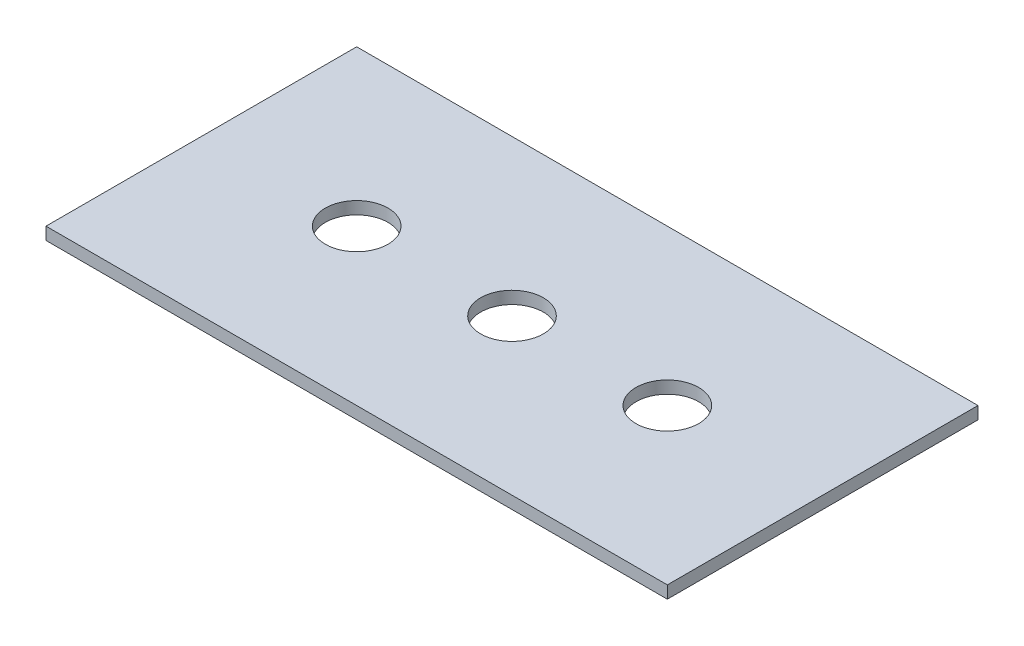
SolidWorks part; units mm, degrees
ref_plane "Front Plane" through (0, 0, 0) normal (0, 0, 1) x (1, 0, 0)
ref_plane "Top Plane" through (0, 0, 0) normal (0, 1, 0) x (1, 0, 0)
ref_plane "Right Plane" through (0, 0, 0) normal (1, 0, 0) x (0, 0, -1)
sketch "Sketch1" plane through (0, 0, 0) normal (0, 1, 0) x (1, 0, 0)
  line L1 (-50.8, -25.4) -> (50.8, -25.4)
  line L2 (-50.8, -25.4) -> (-50.8, 25.4)
  line L3 (-50.8, 25.4) -> (50.8, 25.4)
  line L4 (50.8, -25.4) -> (50.8, 25.4)
  line L5 (0, 25.4) -> (0, -25.4) construction
  line L6 (-50.8, 0) -> (50.8, 0) construction
  point P0 (0, 0)
  dimension "D1" = 50.8
  dimension "D2" = 101.6
extrude "Boss-Extrude1" add sketch "Sketch1" along normal blind 2.032
sketch "Sketch2" plane through (0, 2.032, 0) normal (0, 1, 0) x (1, 0, 0)
  circle A0 centre (0, 0) radius 5.127
  dimension "D1" = 10.254
extrude "Cut-Extrude1" cut sketch "Sketch2" against normal through all
pattern_linear "LPattern1" count 2 spacing 25.4 along (-1, 0, 0) count 2 spacing 25.4 along (1, 0, 0) of "Cut-Extrude1"
equation "\"Arrow Height\"= 1in"
equation "\"Button Height\"= 2in"
equation "\"Button Width\"= 4in"
equation "\"Haptic Diameter\"= 10mm"
equation "\"Haptic Thickness\"= 2.7mm"
equation "\"D1@Sketch1\"=\"Button Height\""
equation "\"D2@Sketch1\"=\"Button Width\""
equation "\"D1@Sketch2\"=\"Haptic Diameter\"+.01in"
